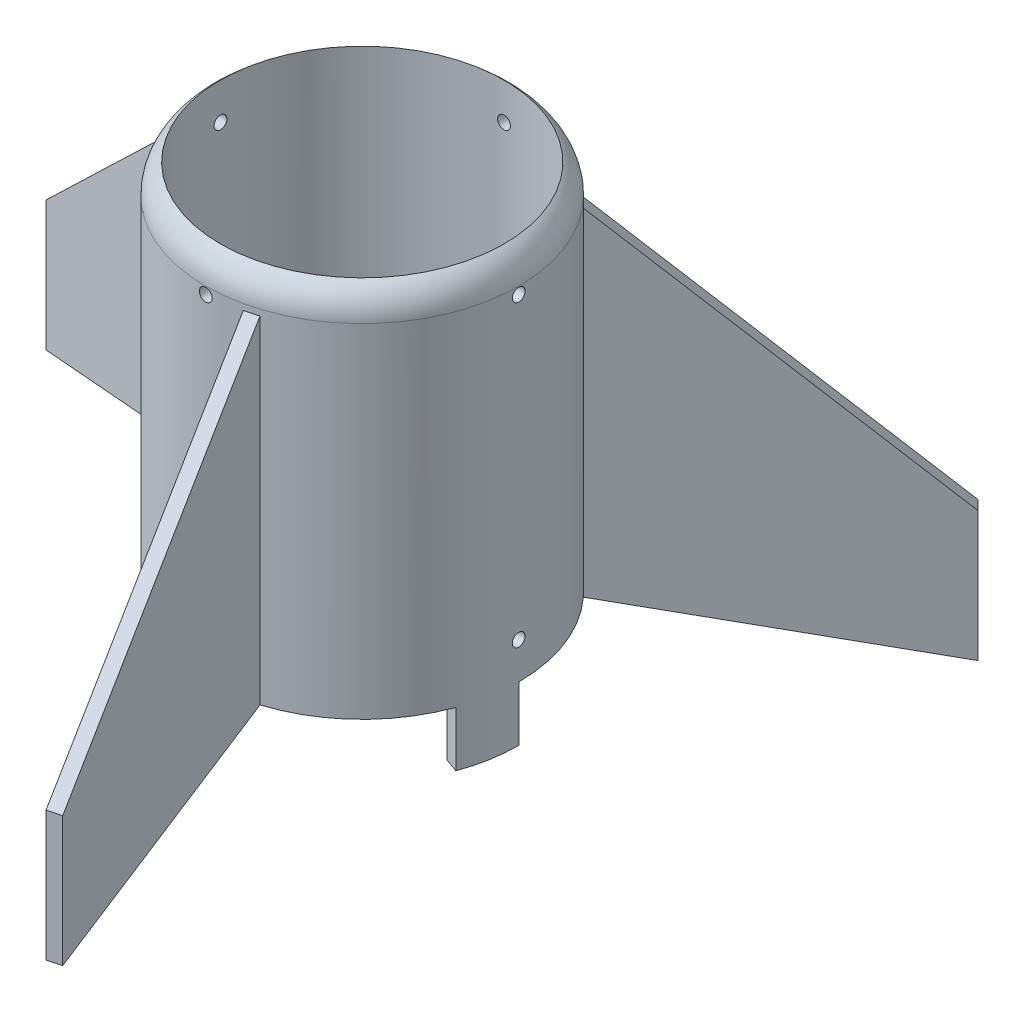
SolidWorks part; units mm, degrees
ref_plane "Front Plane" through (0, 0, 0) normal (0, 0, 1) x (1, 0, 0)
ref_plane "Top Plane" through (0, 0, 0) normal (0, 1, 0) x (1, 0, 0)
ref_plane "Right Plane" through (0, 0, 0) normal (1, 0, 0) x (0, 0, -1)
sketch "Sketch1" plane through (0, 0, 0) normal (0, 1, 0) x (1, 0, 0)
  circle A0 centre (0, 0) radius 38.75
  circle A1 centre (0, 0) radius 42.75
  dimension "D1" = 77.5
  dimension "D2" = 4
extrude "Boss-Extrude1" add sketch "Sketch1" along normal blind 101.6
sketch "Sketch2" plane through (0, 0, 0) normal (0, -1, 0) x (1, 0, 0)
  line L0 (0, 0) -> (40.1719, 14.6214) construction
  line L1 (0, 0) -> (42.75, 0) construction
  line L2 (40.1719, 14.6214) -> (36.4131, 13.2533)
  line L3 (38.75, 0) -> (42.75, 0)
  line L4 (-7.4235, -42.1005) -> (-6.7289, -38.1613)
  line L5 (-19.375, -33.5585) -> (-21.375, -37.0226)
  line L6 (-32.7484, 27.4792) -> (-29.6842, 24.908)
  line L7 (-19.375, 33.5585) -> (-21.375, 37.0226)
  circle A0 centre (0, 0) radius 42.75 construction
  circle A1 centre (0, 0) radius 38.75 construction
  arc A2 (38.75, 0) -> (36.4131, 13.2533) centre (0, 0) ccw
  arc A3 (42.75, 0) -> (40.1719, 14.6214) centre (0, 0) ccw
  arc A4 (-21.375, -37.0226) -> (-7.4235, -42.1005) centre (0, 0) ccw
  arc A5 (-19.375, -33.5585) -> (-6.7289, -38.1613) centre (0, 0) ccw
  arc A6 (-21.375, 37.0226) -> (-32.7484, 27.4792) centre (0, 0) ccw
  arc A7 (-19.375, 33.5585) -> (-29.6842, 24.908) centre (0, 0) ccw
  point P24 (0, 0)
  dimension "D1" = 20
  dimension "D2" = 3
extrude "Boss-Extrude2" add sketch "Sketch2" along normal blind 15
sketch "Sketch3" plane through (0, 0, 0) normal (0, 0, 1) x (1, 0, 0)
  line L0 (0, 0) -> (0, 91.6) construction
  line L1 (42.75, 101.6) -> (-42.75, 101.6) construction
  line L2 (-7.4235, 0) -> (42.75, 0) construction
  circle A0 centre (0, 91.6) radius 1.75
  circle A1 centre (0, 10) radius 1.75
  dimension "D2" = 3.5
  dimension "D1" = 10
  dimension "D3" = 10
extrude "Cut-Extrude1" cut sketch "Sketch3" against normal through all both and the other way through all
sketch "Sketch4" plane through (0, 0, 0) normal (1, 0, 0) x (0, 0, -1)
  line L0 (0, 0) -> (0, 91.6) construction
  line L1 (42.75, 101.6) -> (-42.75, 101.6) construction
  circle A0 centre (0, 91.6) radius 1.75
  circle A1 centre (0, 10) radius 1.75
  dimension "D1" = 3.5
  dimension "D2" = 10
  dimension "D3" = 10
extrude "Cut-Extrude2" cut sketch "Sketch4" against normal through all both and the other way through all
fillet "Fillet1" radius 10 1 edges at (0, 101.6, 42.75)
sketch "Sketch5" plane through (0, 0, 0) normal (0, -1, 0) x (1, 0, 0)
  line L0 (0, 0) -> (30.2288, -30.2288) construction
  line L1 (0, 0) -> (31.5186, -28.8815) construction
  line L2 (0, 0) -> (28.8815, -31.5186) construction
  line L3 (0, 0) -> (0, -2.4889) construction
  line L4 (28.8815, -31.5186) -> (82.763, -85.4001)
  line L5 (31.5186, -28.8815) -> (85.4001, -82.763)
  line L8 (82.763, -85.4001) -> (85.4001, -82.763)
  arc A0 (-7.4235, -42.1005) -> (42.75, 0) centre (0, 0) ccw construction
  arc A1 (28.8815, -31.5186) -> (31.5186, -28.8815) centre (0, 0) ccw
  dimension "D1" = 2.5
  dimension "D2" = 2.5
  dimension "D3" = 45
  dimension "D4" = 76.2
extrude "Boss-Extrude3" add sketch "Sketch5" against normal blind 92
sketch "Sketch6" plane through (1.3186, 0, 1.3186) normal (0.7071, 0, 0.7071) x (0.7071, 0, -0.7071)
  line L0 (118.9093, 92) -> (118.9093, 0) construction
  line L1 (42.7093, 92) -> (118.9093, 20.4737)
  line L4 (42.7093, 92) -> (42.7093, 0) construction
  line L5 (42.7093, 92) -> (118.9093, 92)
  line L6 (118.9093, 92) -> (118.9093, 20.4737)
  point P0 (118.9093, 20.4737)
extrude "Cut-Extrude3" cut sketch "Sketch6" against normal through all
sketch "Sketch7" plane through (1.3186, 0, 1.3186) normal (0.7071, 0, 0.7071) x (0.7071, 0, -0.7071)
  line L0 (42.7093, 0) -> (118.9093, -15)
  line L1 (118.9093, 20.4737) -> (118.9093, -15)
  line L2 (42.7093, 0) -> (118.9093, 20.4737)
  line L3 (-42.75, -15) -> (-41.2933, -15) construction
  point P4 (0, 0)
  point P6 (118.9093, 20.4737)
  point P7 (118.9093, -10.002)
  point P9 (118.9093, -19.2055)
  point P10 (118.9093, -15.6035)
extrude "Boss-Extrude4" add sketch "Sketch7" against normal up to surface (3.7295 mm away) up to face at (55.8222, 28.1184, -58.4594)
pattern_circular "CirPattern2" count 3 over 360 about axis through (0, 0, 0) along (0, 1, 0) of "Boss-Extrude3", "Cut-Extrude3", "Boss-Extrude4"
